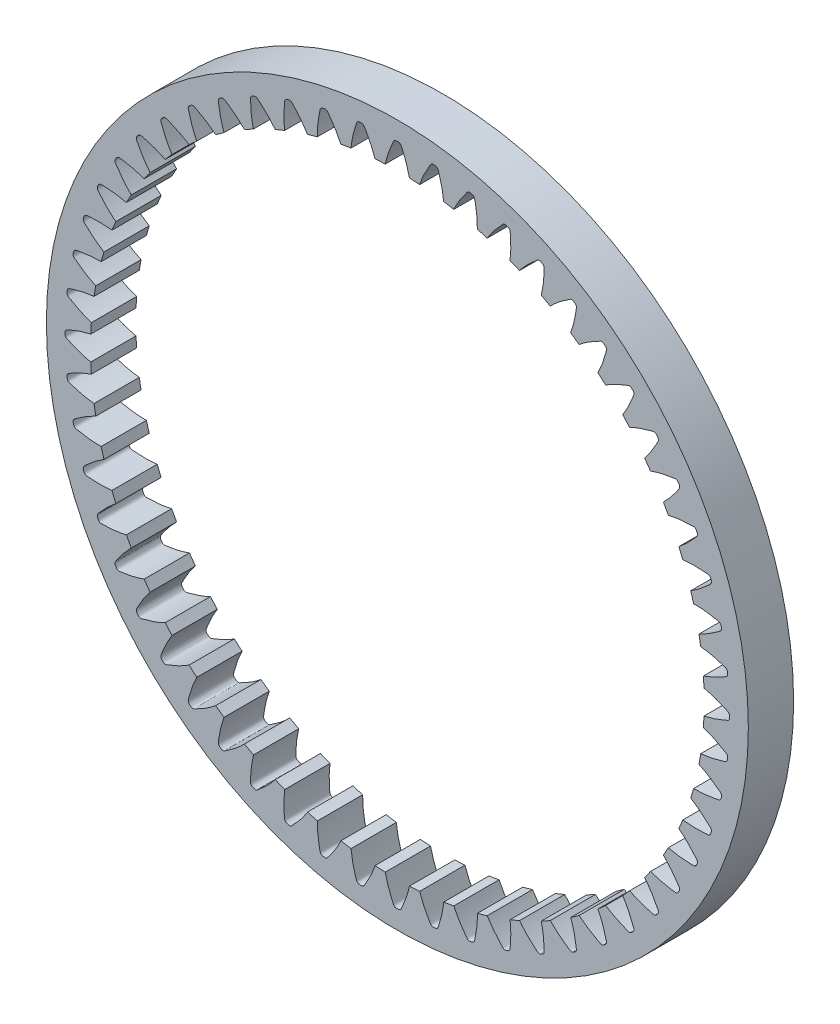
SolidWorks part; units mm, degrees
ref_plane "Front Plane" through (0, 0, 0) normal (0, 0, 1) x (1, 0, 0)
ref_plane "Top Plane" through (0, 0, 0) normal (0, 1, 0) x (1, 0, 0)
ref_plane "Right Plane" through (0, 0, 0) normal (1, 0, 0) x (0, 0, -1)
ref_axis "Axis1" through (0, 0, 55) along (0, 0, -1)
sketch "SketchRevolveSpurGear" plane through (0, 0, 0) normal (1, 0, 0) x (0, 0, -1)
  line L0 (0, 0) -> (1, 0) construction
  line L1 (-2, 27.1) -> (-2, 31)
  line L2 (-2, 31) -> (2, 31)
  line L3 (2, 31) -> (2, 27.1)
  line L4 (2, 27.1) -> (-2, 27.1)
  dimension "Side1" = 2
  dimension "OutsideRadius" = 31
  dimension "Side2" = 2
  dimension "MinorDiameter" = 27.1
revolve "SpurGear" add sketch "SketchRevolveSpurGear" angle 360 about L0
sketch "SketchToothSpurGear" plane through (0, 0, 0) normal (0, 0, 1) x (1, 0, 0)
  arc A0 (27.0633, -1.0714) -> (27.0633, 1.0714) centre (0, 0) ccw
  spline S0 degree 3 poles (27.0633, 1.0714) (27.1716, 1.0494) (27.3402, 1.0108) (27.5725, 0.9492) (27.7665, 0.8928) (27.973, 0.8275) (28.1918, 0.7527) (28.4223, 0.6676) (28.6645, 0.5723) (28.9168, 0.4635) (29.1038, 0.3851) (29.215, 0.3269) (29.2492, 0.3004) (29.279, 0.2701) (29.3043, 0.2358) (29.3244, 0.1983) (29.344, 0.1455) (29.3507, 0.0907) (29.3498, 0.0378) (29.3501, 0) (29.3498, -0.0378) (29.3507, -0.0907) (29.344, -0.1455) (29.3244, -0.1983) (29.3043, -0.2358) (29.279, -0.2701) (29.2492, -0.3004) (29.215, -0.3269) (29.1038, -0.3851) (28.9168, -0.4635) (28.6645, -0.5723) (28.4223, -0.6676) (28.1918, -0.7527) (27.973, -0.8275) (27.7665, -0.8928) (27.5725, -0.9492) (27.3402, -1.0108) (27.1716, -1.0494) (27.0633, -1.0714) knots 0 0 0 0 0.062423 0.097747 0.135813 0.176622 0.220172 0.266463 0.315497 0.367273 0.42179 0.43008 0.438079 0.446078 0.454077 0.462076 0.470075 0.485744 0.492872 0.5 0.507128 0.514256 0.529925 0.537924 0.545923 0.553922 0.561921 0.56992 0.57821 0.632727 0.684503 0.733537 0.779828 0.823378 0.864187 0.902253 0.937577 1 1 1 1
extrude "ToothExtrudeCutSpurGear" cut sketch "SketchToothSpurGear" against normal blind 2 and the other way blind 2
pattern_circular "PatternSpurGear" count 56 every 6.429 about axis through (0, 0, 55) along (0, 0, -1) of "ToothExtrudeCutSpurGear"
sketch "AuxiliarySketchSpurGear" plane through (0, 0, 0) normal (0, 0, 1) x (1, 0, 0)
  circle A0 centre (0, 0) radius 28 construction
  circle A1 centre (0, 0) radius 26.3114 construction
  circle A2 centre (0, 0) radius 29.35 construction
  circle A3 centre (0, 0) radius 27.1 construction
  dimension "PitchDiameter" = 56
  dimension "BaseDiameter" = 52.6228
  dimension "MajorDiameter" = 58.7
  dimension "MinorDiameter" = 54.2
